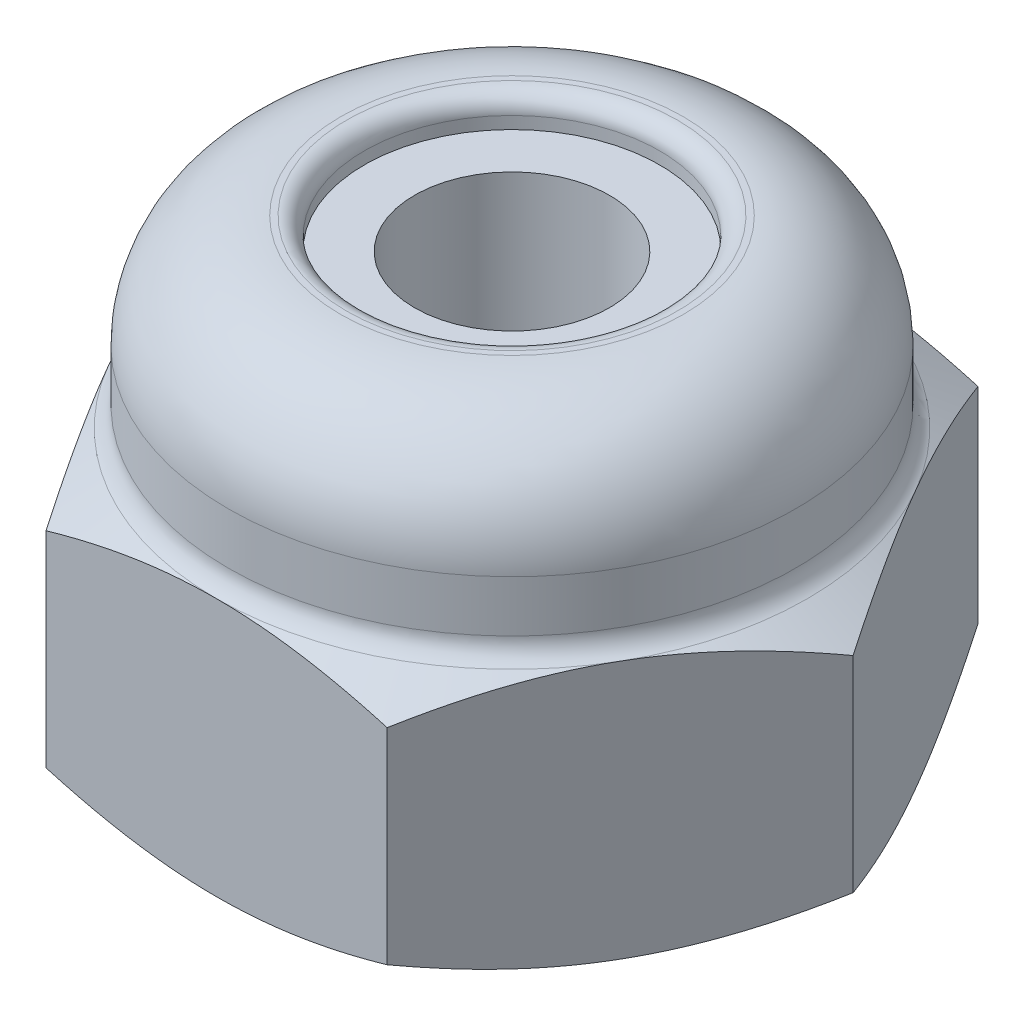
SolidWorks part; units mm, degrees
material "普通碳钢"
ref_plane "前视基准面" through (0, 0, 0) normal (0, 0, 1) x (1, 0, 0)
ref_plane "上视基准面" through (0, 0, 0) normal (0, 1, 0) x (1, 0, 0)
ref_plane "右视基准面" through (0, 0, 0) normal (1, 0, 0) x (0, 0, -1)
sketch "草图1" plane through (0, 0, 0) normal (0, 1, 0) x (1, 0, 0)
  line L1 (2.8868, 0) -> (1.4434, 2.5)
  line L2 (1.4434, 2.5) -> (-1.4434, 2.5)
  line L3 (-1.4434, 2.5) -> (-2.8868, 0)
  line L4 (-2.8868, 0) -> (-1.4434, -2.5)
  line L5 (-1.4434, -2.5) -> (1.4434, -2.5)
  line L6 (1.4434, -2.5) -> (2.8868, 0)
  circle A0 centre (0, 0) radius 2.5 construction
  circle A1 centre (0, 0) radius 1.025
  dimension "D2" = 2.05
extrude "凸台-拉伸1" add sketch "草图1" along normal mid plane 2.3
sketch "草图4" plane through (0, 0, 0) normal (1, 0, 0) x (0, 0, -1)
  line L0 (0, 2.8045) -> (0, -1.6258) construction
  line L1 (-2.4, 1.15) -> (-2.4, 2.65)
  line L2 (0, 1.15) -> (-2.5, 1.15) construction
  line L3 (-2.4, 2.65) -> (-1.25, 2.65)
  line L4 (-1.25, 2.65) -> (-1.25, 2.3967)
  line L5 (-1.25, 2.3967) -> (-1.75, 2.3967)
  line L6 (-1.75, 2.3967) -> (-1.75, 1.15)
  line L7 (-1.75, 1.15) -> (-2.4, 1.15)
  line L8 (0, -1.15) -> (-2.5, -1.15) construction
  dimension "D1" = 4.8
  dimension "D2" = 3.8
  dimension "D3" = 3.5
  dimension "D4" = 0.2533
  dimension "D5" = 2.5
revolve "旋转1" add sketch "草图4" angle 360 about L0
sketch "草图5" plane through (0, 0, 0) normal (1, 0, 0) x (0, 0, -1)
  line L0 (0, 2.5136) -> (0, -1.2831) construction
  line L1 (-2.5, 1.15) -> (0, 1.15) construction
  line L2 (-1.75, 2.3867) -> (-0.825, 2.3867)
  line L3 (-1.75, 2.3867) -> (-1.75, 1.15)
  line L4 (-1.75, 1.15) -> (-0.825, 1.15)
  line L5 (-0.825, 2.3867) -> (-0.825, 1.15)
  line L6 (-1.75, 2.3967) -> (-1.75, 1.15) construction
  line L7 (-1.25, 2.3967) -> (-1.75, 2.3967) construction
  dimension "D1" = 1.65
revolve "旋转2" add sketch "草图5" angle 360 about L0
fillet "圆角1" radius 0.95 1 edges at (0, 2.65, 2.4)
fillet "圆角3" radius 0.15 1 edges at (0, 2.65, 1.25)
sketch "草图6" plane through (0, 0, 0) normal (1, 0, 0) x (0, 0, -1)
  line L0 (0, 2.5376) -> (0, -1.7712) construction
  line L1 (-2.5233, 0) -> (2.9538, 0) construction
  line L2 (2.4, 1.15) -> (4.3053, 1.15)
  line L3 (4.3053, 1.15) -> (4.3053, 0.05)
  line L4 (4.3053, 0.05) -> (2.4, 1.15)
  line L5 (4.3053, -0.05) -> (2.4, -1.15)
  line L6 (4.3053, -1.15) -> (4.3053, -0.05)
  line L7 (2.4, -1.15) -> (4.3053, -1.15)
  line L9 (2.5, 1.15) -> (2.5, -1.15) construction
  line L10 (-2.5, 1.15) -> (0, 1.15) construction
  dimension "D1" = 30
  dimension "D2" = 0.1
  dimension "D3" = 0.1
revolve "切除-旋转1" cut sketch "草图6" angle 360 about L0
fillet "圆角4" radius 0.2 1 edges at (0, 1.15, 2.4)
fillet "圆角5" radius 0.3 1 edges at (0, -1.15, 2.4)
chamfer "倒角1" distance 0.1 angle 45 1 edges at (0, -1.15, 1.025)
move or copy body "实体-移动/复制3" [suppressed] bodies to move or copy 109
move or copy body "实体-移动/复制4" [suppressed] bodies to move or copy 112
move or copy body "实体-移动/复制2" [suppressed] bodies to move or copy 109
move or copy body "实体-移动/复制1" [suppressed] bodies to move or copy 109
equation "\"规格\"= 2"
equation "\"螺距\"= 0.4"
equation "\"孔径\"= \"规格\" - \"螺距\""
equation "\"h\"= 3"
equation "\"m\"= 2"
equation "\"s\"= 4"
equation "\"D1@草图1\"=\"s\""
equation "\"D2@草图1\"=\"孔径\""
equation "\"D1@凸台-拉伸1\"=\"m\""
equation "\"D1@草图4\"=\"s\"-0.2"
equation "\"D2@草图4\"=\"h\""
equation "\"D3@草图4\"=\"规格\"+1"
equation "\"D4@草图4\"=\"h\"/15"
equation "\"D5@草图4\"=\"规格\"+0.2"
equation "\"D1@草图5\"=\"规格\"-0.6"
